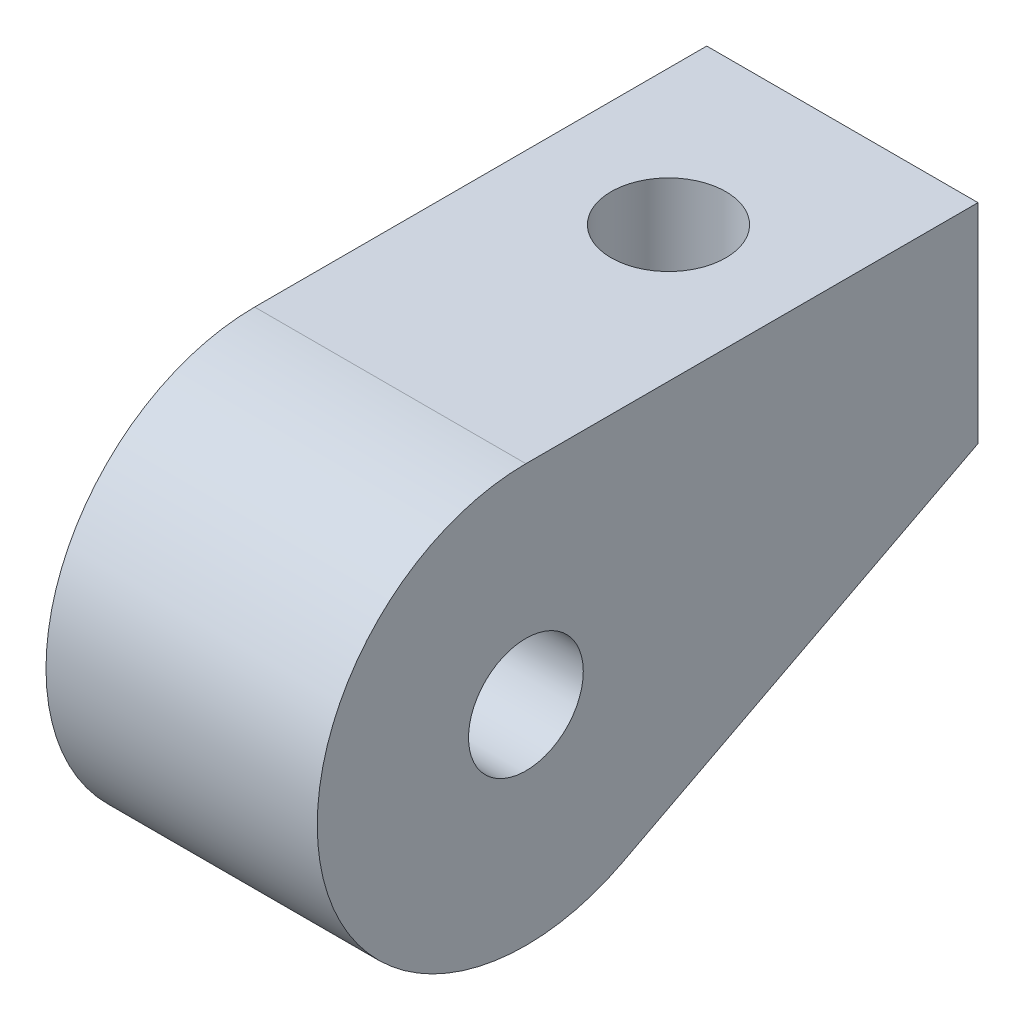
SolidWorks part; units mm, degrees
ref_plane "Front Plane" through (0, 0, 0) normal (0, 0, 1) x (1, 0, 0)
ref_plane "Top Plane" through (0, 0, 0) normal (0, 1, 0) x (1, 0, 0)
ref_plane "Right Plane" through (0, 0, 0) normal (1, 0, 0) x (0, 0, -1)
sketch "Sketch1" plane through (0, 0, 0) normal (1, 0, 0) x (0, 0, -1)
  line L0 (0, 6) -> (13, 6)
  line L1 (13, 6) -> (13, -6)
  line L2 (13, -6) -> (0, -6) construction
  line L3 (8, 6) -> (8, -6) construction
  line L4 (2.7692, -5.3227) -> (13, 0)
  circle A0 centre (0, 0) radius 1.65
  circle A1 centre (0, 0) radius 6
  dimension "D1" = 3.3
  dimension "D2" = 12
  dimension "D3" = 8
  dimension "D4" = 5
extrude "Boss-Extrude1" add sketch "Sketch1" along normal mid plane 7.8 contours A1 A0 region at (0, 4.1226, -4.1226)
extrude "Boss-Extrude2" add sketch "Sketch1<4>" along normal mid plane 7.8 contours L3 L0 A1 L2 | L0 L3 L2 L1 region at (0, 2.1549, -8.549)
sketch "Sketch1<4>" plane through (0, 0, 0) normal (1, 0, 0) x (0, 0, -1) same geometry as "Sketch1"
sketch "Sketch2" plane through (0, 6, 0) normal (0, 1, 0) x (1, 0, 0)
  circle A0 centre (0, 8) radius 1.65
  dimension "D1" = 3.3
extrude "Cut-Extrude5" cut sketch "Sketch2" against normal through all
sketch "Sketch3" plane through (0, 6, 0) normal (0, -1, 0) x (1, 0, 0)
  line L1 (0, -11.3) -> (2.8579, -9.65)
  line L2 (2.8579, -9.65) -> (2.8579, -6.35)
  line L3 (2.8579, -6.35) -> (0, -4.7)
  line L4 (0, -4.7) -> (-2.8579, -6.35)
  line L5 (-2.8579, -6.35) -> (-2.8579, -9.65)
  line L6 (-2.8579, -9.65) -> (0, -11.3)
  circle A0 centre (0, -8) radius 2.8579 construction
  dimension "D1" = 3.3
extrude "Cut-Extrude6" cut sketch "Sketch3" along normal through all from offset 4
sketch "Sketch4" plane through (0, 6, 0) normal (0, -1, 0) x (1, 0, 0)
  circle A0 centre (0, -8) radius 2.097
